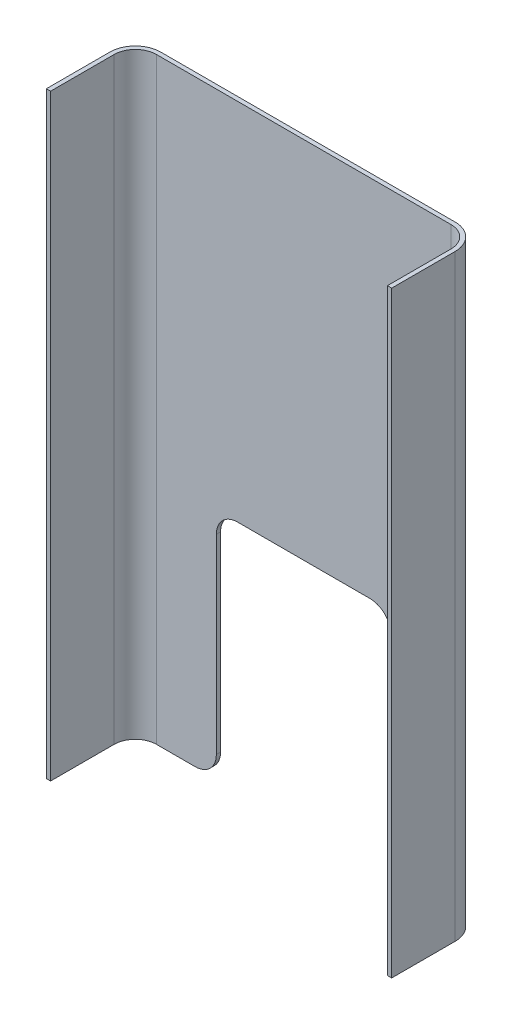
SolidWorks part; units mm, degrees
material "Polycarbonate, Black"
ref_plane "Front Plane" through (0, 0, 0) normal (0, 0, 1) x (1, 0, 0)
ref_plane "Top Plane" through (0, 0, 0) normal (0, 1, 0) x (1, 0, 0)
ref_plane "Right Plane" through (0, 0, 0) normal (1, 0, 0) x (0, 0, -1)
sketch "Sketch1" plane through (0, 0, 0) normal (0, 1, 0) x (1, 0, 0)
  line L0 (-159, -80) -> (-159, -20)
  line L1 (-139, 0) -> (139, 0)
  line L2 (159, -20) -> (159, -80)
  arc A0 (139, 0) -> (159, -20) centre (139, -20) cw
  arc A1 (-159, -20) -> (-139, 0) centre (-139, -20) cw
  dimension "D1" = 20
  dimension "D2" = 318
  dimension "D3" = 80
extrude "Extrude-Thin1" add sketch "Sketch1" along normal blind 564 thin thin type one direction reverse wall 4
sketch "Sketch2" plane through (0, 0, -4) normal (0, 0, -1) x (-1, 0, 0)
  line L0 (139, 0) -> (-139, 0) construction
  line L1 (-82.5, -85.2671) -> (82.5, -85.2671)
  line L2 (-82.5, -85.2671) -> (-82.5, 175)
  line L3 (-82.5, 175) -> (82.5, 175)
  line L4 (82.5, -85.2671) -> (82.5, 175)
  line L5 (0, 0) -> (0, 175) construction
  dimension "D1" = 175
  dimension "D2" = 165
extrude "Cut-Extrude1" [suppressed] cut sketch "Sketch2" against normal through all both and the other way through all
sketch "Sketch3" plane through (0, 0, -4) normal (0, 0, -1) x (-1, 0, 0)
  line L0 (139, 0) -> (-139, 0) construction
  line L1 (-82.5, 0) -> (82.5, 0)
  line L2 (-82.5, 0) -> (-82.5, 220)
  line L3 (-82.5, 220) -> (82.5, 220)
  line L4 (82.5, 0) -> (82.5, 220)
  dimension "D1" = 165
  dimension "D2" = 220
extrude "Cut-Extrude2" cut sketch "Sketch3" against normal through all both and the other way through all
fillet "Fillet1" radius 20 4 edges at (82.5, 220, -2) (-82.5, 220, -2) (-82.5, 0, -2) (82.5, 0, -2)
fillet "Fillet2" [suppressed] radius 10
fillet "Fillet3" [suppressed] radius 20
